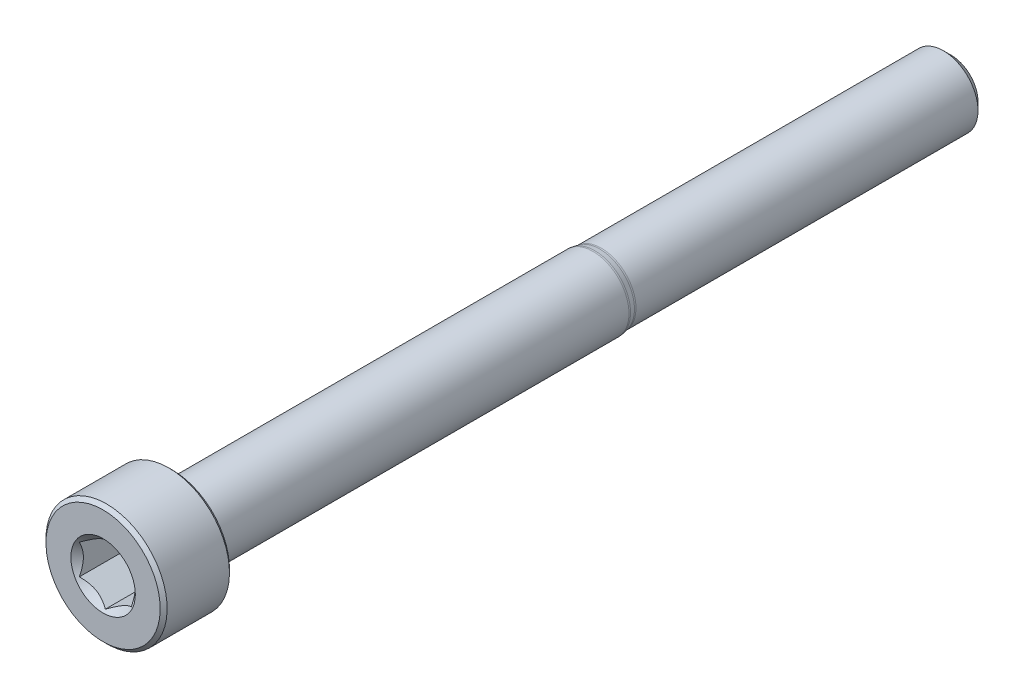
SolidWorks part; units mm, degrees
material "Alloy Steel"
ref_plane "Front Plane" through (0, 0, 0) normal (0, 0, 1) x (1, 0, 0)
ref_plane "Top Plane" through (0, 0, 0) normal (0, 1, 0) x (1, 0, 0)
ref_plane "Right Plane" through (0, 0, 0) normal (1, 0, 0) x (0, 0, -1)
sketch "Sketch1" plane through (0, 0, 0) normal (1, 0, 0) x (0, 0, -1)
  line L0 (-24.5, 0) -> (24.5, 0) construction
  line L1 (24.5, 0) -> (24.5, 1.5453) construction
  line L2 (24.5, 1.5453) -> (24.0453, 2) construction
  line L3 (24.0453, 2) -> (23.975, 2) construction
  line L4 (23.975, 2) -> (-20.5, 2) construction
  line L5 (-20.5, 2) -> (-20.5, 3.5) construction
  line L6 (-20.5, 3.5) -> (-24.5, 3.5) construction
  line L7 (-24.5, 3.5) -> (-24.5, 0) construction
  line L8 (24.5, 1.5453) -> (24.5, 2) construction
  line L9 (24.4562, 2.0758) -> (24.8062, 1.4696) construction
  line L10 (24.8062, 1.4696) -> (25.1562, 2.0758) construction
  line L11 (25.1562, 2.0758) -> (24.4562, 2.0758) construction
  line L12 (24.8062, 2.0758) -> (24.8062, 2) construction
  line L13 (24.8062, 1.4696) -> (24.8062, 1.5453) construction
  line L14 (24.7625, 1.5453) -> (24.85, 1.5453) construction
  line L15 (24.5, 2) -> (25.1125, 2) construction
  line L16 (24.4781, 2.0379) -> (25.1344, 2.0379) construction
  line L17 (24.5, 0) -> (24.5, -2) construction
  line L18 (-20.7, 3.5) -> (-20.5, 3.3) construction
  line L19 (-24.3, 3.5) -> (-24.5, 3.3) construction
  line L20 (-20.5, 2) -> (-20.5, 0) construction
  line L21 (-20.5, 1) -> (-5.5, 1) construction
  line L22 (-5.5, 1) -> (9.5, 1) construction
  line L23 (9.5, 1) -> (24.5, 1) construction
  line L24 (-5.5, 1) -> (-5.5, 2) construction
  line L25 (-5.5, 2) -> (-5.5, 3.5) construction
  line L26 (9.5, 1) -> (9.5, 3.5) construction
  point P0 (-24.5, 1.5)
  point P3 (22.75, 2)
  point P4 (0, 0)
  point P18 (9.5, 2)
  point P22 (24.8062, 1.5453)
  point P24 (23.975, 2)
  point P25 (24.8062, 2)
  point P28 (24.8062, 2.0379)
  point P29 (22.75, -2)
  point P30 (-5.5, 2)
  point P31 (-22.5, 3.5)
  point P37 (-21.2, 3.5)
  point P38 (-24.2, 3.5)
  point P45 (-5.5, 1)
  point P46 (9.5, 1)
  point P49 (4.5, 2)
  dimension "D1" = 45
  dimension "D2" = 0.0875
  dimension "D7" = 0.2
  dimension "D8" = 0.2
  dimension "D9" = 0.2
  dimension "D10" = 0.1
  dimension "D11" = 0.5
  dimension "Drive Size" = 3
  dimension "Head Diameter" = 7
  dimension "Head Height" = 4
  dimension "Thread Pitch" = 0.7
  dimension "Thread Dia" = 4
  dimension "Length" = 45
  dimension "D12" = 0.525
  dimension "D4" = 1.75
  dimension "Minimum Thread Length" = 20
  dimension "D3" = 25
sketch "Sketch2" plane through (0, 0, 0) normal (1, 0, 0) x (0, 0, -1)
  line L0 (-24.5, 0) -> (-24.5, 3.3)
  line L1 (-24.3, 3.5) -> (-20.7, 3.5)
  line L2 (-20.5, 3.3) -> (-20.5, 2.2758)
  line L4 (24.0453, 2) -> (24.5, 1.5453)
  line L5 (24.5, 1.5453) -> (24.5, 0)
  line L6 (-20.5, 3.5) -> (-24.5, 3.5) construction
  line L7 (24.5, 0) -> (-24.5, 0)
  line L8 (-24.3, 3.5) -> (-24.5, 3.3) construction
  line L10 (-24.3, 3.5) -> (-24.5, 3.3)
  line L14 (-20.7, 3.5) -> (-20.5, 3.3) construction
  line L16 (-20.7, 3.5) -> (-20.5, 3.3)
  line L17 (-20.5, 2) -> (-20.5, 3.5) construction
  line L18 (-20.3, 2.0758) -> (3.8073, 2.0758)
  line L19 (4.2867, 2) -> (24.0453, 2)
  line L20 (23.975, 2) -> (-20.5, 2) construction
  line L21 (3.9048, 2.0662) -> (4.1892, 2.0096)
  line L22 (25.1562, 2.0758) -> (24.4562, 2.0758) construction
  arc A1 (-20.5, 2.2758) -> (-20.3, 2.0758) centre (-20.3, 2.2758) ccw
  arc A2 (3.8073, 2.0758) -> (3.9048, 2.0662) centre (3.8073, 1.5758) cw
  arc A3 (4.1892, 2.0096) -> (4.2867, 2) centre (4.2867, 2.5) ccw
  point P39 (4.2375, 2)
  dimension "D3" = 0.2
  dimension "D6" = 0.5
  dimension "D4" = 11.25
  dimension "D5" = 0.2625
revolve "Revolve1" add sketch "Sketch2" angle 360 about L7
sketch "Sketch3" plane through (0, 0, 24.5) normal (0, 0, 1) x (1, 0, 0)
  line L1 (1.5, -0.866) -> (1.5, 0.866)
  line L2 (1.5, 0.866) -> (0, 1.7321)
  line L3 (0, 1.7321) -> (-1.5, 0.866)
  line L4 (-1.5, 0.866) -> (-1.5, -0.866)
  line L5 (-1.5, -0.866) -> (0, -1.7321)
  line L6 (0, -1.7321) -> (1.5, -0.866)
  circle A0 centre (0, 0) radius 1.5 construction
  circle A1 centre (0, 0) radius 3.5 construction
  circle A2 centre (0, 0) radius 3.5 construction
  circle A3 centre (0, 0) radius 1.7321 construction
  dimension "D1" = 3.4641
extrude "Cut-Extrude1" cut sketch "Sketch3" against normal offset from surface (3 mm away) 1 up to face at (0, 3.3, 20.5)
sketch "Sketch4" plane through (0, 0, 24.5) normal (0, 0, 1) x (1, 0, 0)
  circle A0 centre (0, 0) radius 1.862
  dimension "D1" = 3.7239
extrude "Cut-Extrude2" cut sketch "Sketch4" against normal up to vertex (2 mm away) draft 45 up to point (0, 3.5, 22.5)
sketch "Sketch11" plane through (0, 0, 0) normal (1, 0, 0) x (0, 0, -1)
  line L0 (-24.5, 0) -> (24.5, 0) construction
  line L1 (-24.5, 0) -> (24.5, 0) construction
  line L2 (-18.3125, 0) -> (-18.3125, 2) construction
  line L3 (23.975, 2) -> (-20.5, 2) construction
  line L4 (1.6198, 0) -> (1.6198, 2) construction
  point P2 (-18.3125, 0)
  point P3 (1.6198, 0)
  dimension "D1" = 2.1875
  dimension "D2" = 2.1875
sketch "Sketch6" [suppressed] plane through (0, 0, -24.5) normal (0, 0, -1) x (-1, 0, 0)
  circle A0 centre (0, 0) radius 2
curve "Helix/Spiral1" [suppressed] pitch 0.7 height 20.7 turns 29.5714
sketch "Sketch10" [suppressed] plane through (0, 0, 0) normal (1, 0, 0) x (0, 0, -1)
  line L0 (4.5, -2) -> (4.5, 2)
  line L2 (-24.5, 0) -> (24.5, 0) construction
  point P3 (4.5, 0)
split "Split1" [suppressed] bodies to split 106
sketch "Sketch7" [suppressed] plane through (0, 0, 0) normal (1, 0, 0) x (0, 0, -1)
  line L0 (24.4781, 2.0379) -> (25.1344, 2.0379)
  line L1 (25.1344, 2.0379) -> (24.85, 1.5453)
  line L2 (24.85, 1.5453) -> (24.7625, 1.5453)
  line L3 (24.7625, 1.5453) -> (24.4781, 2.0379)
sweep "Cut-Sweep1" [suppressed] cut profiles "Sketch7" path "Helix/Spiral1"
sketch "Sketch8" [suppressed] plane through (0, 0, 0) normal (1, 0, 0) x (0, 0, -1)
  line L0 (-20.5, 0) -> (-20.5, 2)
  line L2 (-20.5, 2) -> (4.5, 2)
  line L4 (4.5, 2) -> (5.6547, 0)
  line L5 (5.6547, 0) -> (-20.5, 0)
  line L6 (23.975, 2) -> (-20.5, 2) construction
  line L7 (-24.5, 0) -> (24.5, 0) construction
  dimension "D1" = 60
  dimension "D2" = 20
revolve "Revolve2" [suppressed] add sketch "Sketch8" angle 360 about L5
equation "\"D2@Sketch1\" = \"Thread Pitch@Sketch1\" / 8"
equation "\"D4@Helix/Spiral1\" = \"Thread Pitch@Sketch1\""
equation "\"D7@Sketch1\" = \"Head Height@Sketch1\" * .05"
equation "\"D8@Sketch1\"=\"D7@Sketch1\""
equation "\"D9@Sketch1\"=\"D7@Sketch1\""
equation "\"D10@Sketch1\"=\"D7@Sketch1\"/2"
equation "\"D11@Sketch1\"=\"D10@Sketch1\"*5"
equation "\"D4@Sketch1\"=\"Thread Pitch@Sketch1\"*2.5"
equation "\"D12@Sketch1\"=\"Thread Pitch@Sketch1\"*.75"
equation "\"D3@Helix/Spiral1\"=\"Minimum Thread Length@Sketch1\"+\"Thread Pitch@Sketch1\""
equation "\"D2@Sketch8\"=\"Minimum Thread Length@Sketch1\""
equation "\"D3@Sketch2\"=\"Thread Dia@Sketch1\"*0.05"
equation "\"D5@Sketch2\"=\"D12@Sketch1\"*0.5"
equation "\"D6@Sketch2\"=\"Thread Dia@Sketch1\"*0.125"
equation "\"D1@Sketch11\"=\"D3@Sketch1\"*0.0875"
equation "\"D2@Sketch11\"=\"D1@Sketch11\""
equation "\"D1@Sketch4\"=\"D1@Sketch3\"*1.075"
